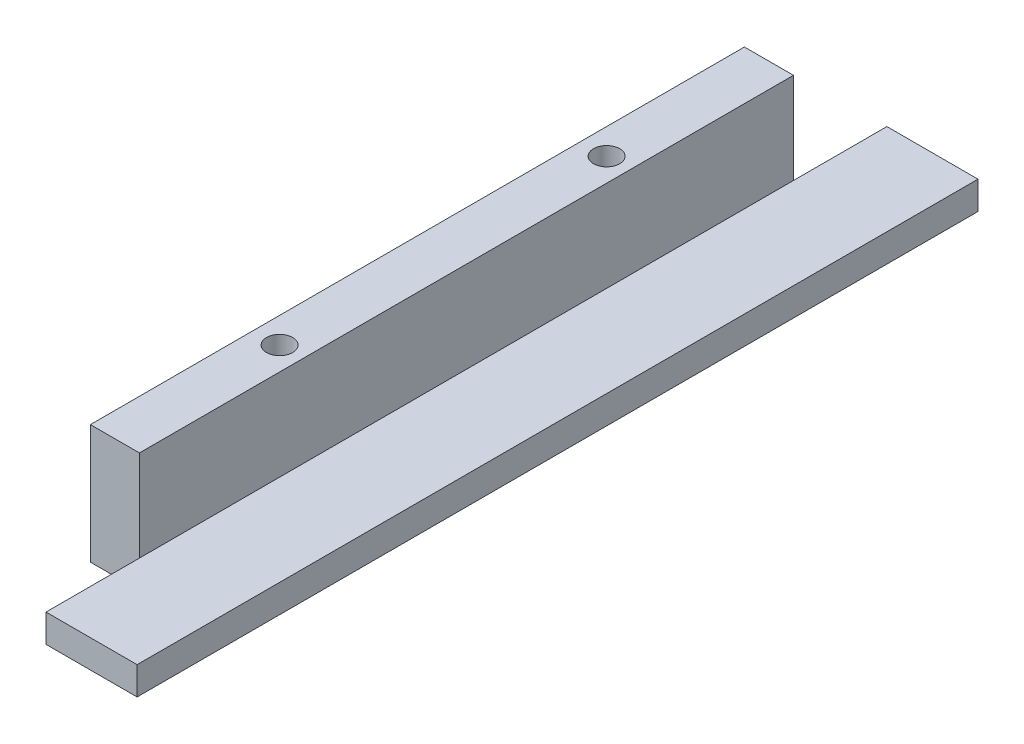
SolidWorks part; units mm, degrees
ref_plane "Płaszczyzna przednia" through (0, 0, 0) normal (0, 0, 1) x (1, 0, 0)
ref_plane "Płaszczyzna górna" through (0, 0, 0) normal (0, 1, 0) x (1, 0, 0)
ref_plane "Płaszczyzna prawa" through (0, 0, 0) normal (1, 0, 0) x (0, 0, -1)
sketch "Szkic1" plane through (0, 0, 0) normal (0, 0, 1) x (1, 0, 0)
  line L0 (9.75, -9.75) -> (9.75, -15.75)
  line L1 (-9.75, -9.75) -> (9.75, -9.75)
  line L2 (-9.75, -9.75) -> (-9.75, 9.75)
  line L3 (-9.75, 9.75) -> (9.75, 9.75)
  line L4 (9.75, -9.75) -> (9.75, 9.75)
  line L5 (-9.75, -9.75) -> (9.75, 9.75) construction
  line L6 (-9.75, 9.75) -> (9.75, -9.75) construction
  line L7 (9.75, -15.75) -> (-20.25, -15.75)
  line L8 (-20.25, -15.75) -> (-20.25, 9.75)
  line L9 (-20.25, 9.75) -> (-9.75, 9.75)
  point P0 (0, 0)
  dimension "D1" = 19.5
  dimension "D2" = 30
  dimension "D3" = 6
extrude "Dodanie-wyciągnięcie1" add sketch "Szkic1" along normal blind 180 contours L8 L7 L0 L1 L2 L3 region at (-10.4386, -5.9649, 0)
ref_plane "Płaszczyzna1" through (0, 0, 90) normal (0, 0, 1) x (1, 0, 0)
sketch "Szkic2" plane through (0, 9.75, 0) normal (0, 1, 0) x (1, 0, 0)
  line L0 (-9.75, -180) -> (-9.75, 0) construction
  line L1 (-20.25, -180) -> (-9.75, -180)
  line L2 (-20.25, -180) -> (-20.25, -160)
  line L3 (-20.25, -160) -> (-9.75, -160)
  line L4 (-9.75, -180) -> (-9.75, -160)
  dimension "D1" = 20
extrude "Wytnij-wyciągnięcie1" cut sketch "Szkic2" against normal through all
mirror "Lustro1" about plane through (0, 0, 90) normal (0, 0, 1) of "Wytnij-wyciągnięcie1"
sketch "Szkic3" plane through (0, 9.75, 0) normal (0, 1, 0) x (1, 0, 0)
  line L0 (-9.75, -160) -> (-9.75, -20) construction
  line L2 (-9.75, -20) -> (-20.25, -20) construction
  circle A0 centre (-14.75, -55) radius 2.8
  circle A1 centre (-14.75, -125) radius 2.8
  dimension "D1" = 5.6
  dimension "D2" = 5
  dimension "D3" = 70
  dimension "D4" = 35
extrude "Wytnij-wyciągnięcie2" cut sketch "Szkic3" against normal blind 10
